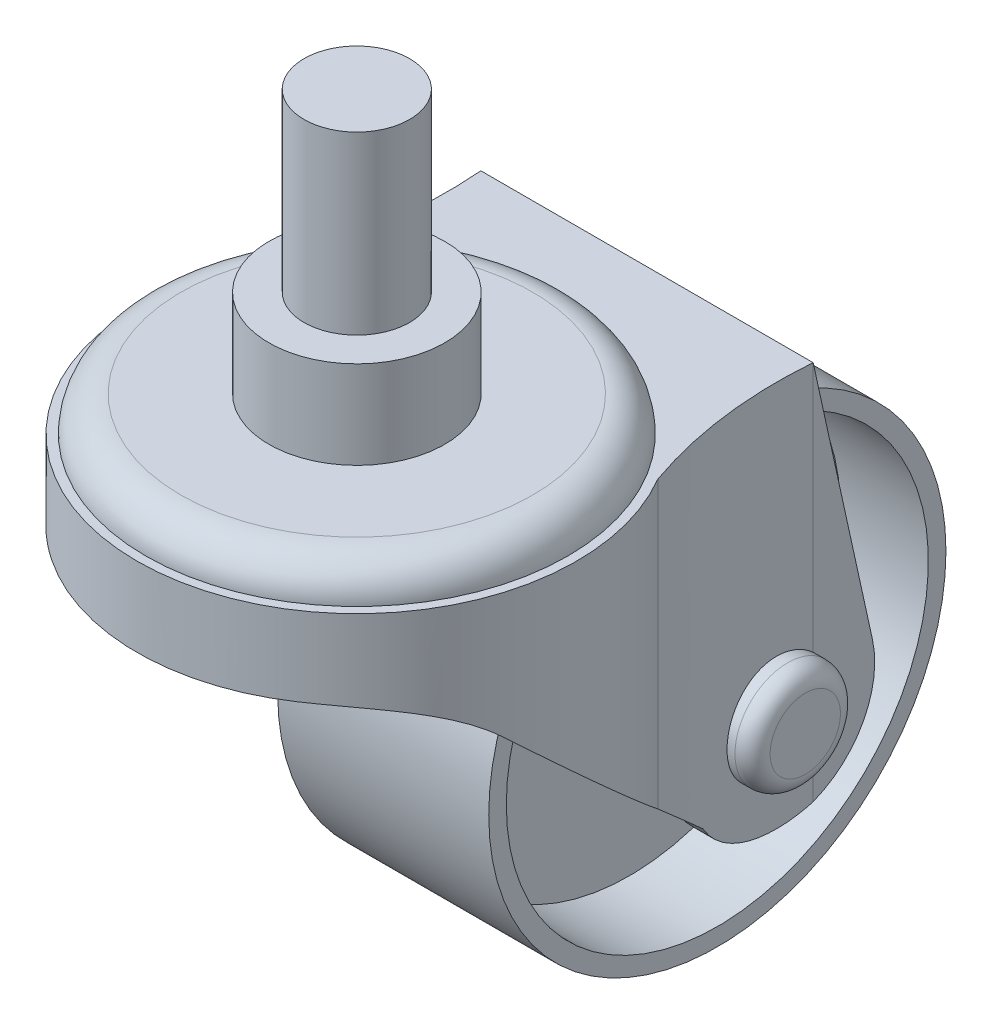
SolidWorks part; units mm, degrees
ref_plane "Plan de face" through (0, 0, 0) normal (0, 0, 1) x (1, 0, 0)
ref_plane "Plan de dessus" through (0, 0, 0) normal (0, 1, 0) x (1, 0, 0)
ref_plane "Plan de droite" through (0, 0, 0) normal (1, 0, 0) x (0, 0, -1)
sketch "Esquisse1" plane through (0, 0, 0) normal (1, 0, 0) x (0, 0, -1)
  line L0 (5.3714, 1.1823) -> (2, 16.5)
  line L1 (2, 16.5) -> (-27, 16.5)
  line L3 (-27, 16.5) -> (-27, 12)
  line L4 (-27, 12) -> (-24.8813, 12)
  line L5 (-18.135, 9.3815) -> (-4.6413, -2.951)
  arc A0 (-4.6413, -2.951) -> (5.3714, 1.1823) centre (0, 0) ccw
  arc A1 (-18.135, 9.3815) -> (-24.8813, 12) centre (-24.8813, 2) ccw
  point P11 (-21, 12)
  dimension "D1" = 11
  dimension "D2" = 16.5
  dimension "D7" = 10
  dimension "D3" = 2
  dimension "D4" = 29
  dimension "D5" = 4.5
  dimension "D6" = 6
extrude "BASE" add sketch "Esquisse1" along normal blind 25
sketch "Esquisse2" plane through (0, 16.5, 0) normal (0, 1, 0) x (1, 0, 0)
  line L0 (0, -27) -> (25, 5.6712) construction
  line L1 (12.5, -10.6644) -> (12.5, -22.6672) construction
  line L2 (25, -27) -> (0, -27) construction
  line L3 (12.4486, -2) -> (21.9486, -2) construction
  line L4 (25, 2) -> (0, 2) construction
  line L5 (21.9486, -2) -> (21.9486, 2) construction
  line L6 (21.9486, 2) -> (21.9486, 5.6712)
  line L7 (0, 5.6712) -> (25, 5.6712)
  line L8 (0, 5.6712) -> (0, -27)
  line L9 (0, -27) -> (25, -27)
  line L10 (25, 5.6712) -> (25, -27)
  line L11 (0, 5.6712) -> (25, -27) construction
  line L12 (0, -27) -> (25, 5.6712) construction
  line L13 (3.0514, 2) -> (3.0514, 5.6712)
  arc A0 (1.7322, -8.1515) -> (23.2678, -8.1515) centre (12.5, -14.5) ccw
  spline S0 degree 2 poles (23.2678, -8.1515) (21.5292, -3.1901) (21.9486, 2) knots 0 0 0 1 1 1
  spline S1 degree 2 poles (1.7322, -8.1515) (3.4708, -3.1901) (3.0514, 2) knots 0 0 0 1 1 1
  line M1 (0, 2) -> (0, -27)
  line M2 (0, -27) -> (25, -27)
  line M3 (25, -27) -> (25, 2)
  line M4 (25, 2) -> (0, 2)
  dimension "D1" = 25
  dimension "D2" = 9.5
  dimension "D3" = 4
extrude "VIDE BASE" cut sketch "Esquisse2" against normal blind 25 contours S0 A0 L10 M4 | L10 L7 L6 M4 | L13 L7 L8 M4 | A0 S1 M4 M1 | A0 L8 M2 | A0 L9 M3 region at (23.6921, 16.5, 3.4682) region at (23.4743, 16.5, -3.8356) region at (1.5257, 16.5, -3.8356) region at (1.3079, 16.5, 3.4682) region at (22.2079, 16.5, 24.2079) region at (2.7921, 16.5, 24.2079)
sketch "Esquisse3" plane through (0, 16.5, 0) normal (0, 1, 0) x (1, 0, 0)
  line L0 (25, -14.5) -> (0, -14.5) construction
  arc A0 (1.7322, -8.1515) -> (23.2678, -8.1515) centre (12.5, -14.5) ccw construction
  circle A1 centre (12.5, -14.5) radius 12
  dimension "D1" = 24
ref_plane "AXE DE SYM" through (12.5, 0, 0) normal (-1, 0, 0) x (0, 0, 1)
sketch "Esquisse4" plane through (12.5, 0, 0) normal (-1, 0, 0) x (0, 0, 1)
  line L0 (14.5, 16.5) -> (14.5, 33.5)
  line L1 (14.5, 33.5) -> (17.5, 33.5)
  line L2 (17.5, 33.5) -> (17.5, 23.5)
  line L3 (17.5, 23.5) -> (19.5, 23.5)
  line L4 (19.5, 23.5) -> (19.5, 18.5)
  line L5 (19.5, 18.5) -> (26.5, 18.5)
  line L6 (26.5, 18.5) -> (26.5, 16.5)
  line L7 (26.5, 16.5) -> (14.5, 16.5)
  dimension "D1" = 12
  dimension "D2" = 2
  dimension "D3" = 5
  dimension "D4" = 10
  dimension "D5" = 3
  dimension "D6" = 2
revolve "VIS" add sketch "Esquisse4" angle 360 about L0
fillet "Congé2" radius 2 1 edges at (12.5, 18.5, 2.5)
sketch "Esquisse6" plane through (0, 0, 0) normal (0, 1, 0) x (1, 0, 0)
  line L0 (12.5, 17.3057) -> (12.5, -17.3057) construction
  line L1 (4.0514, 5.5) -> (4.0514, -5.6095)
  line L2 (21.9486, 5.5) -> (3.0514, 5.5) construction
  line L3 (4.0514, 5.5) -> (20.9486, 5.5)
  line L4 (20.9486, 5.5) -> (20.9486, -5.6095)
  line L5 (3.0514, 5.5) -> (3.0514, 2) construction
  line L6 (21.9486, 2) -> (21.9486, 5.5) construction
  arc A0 (4.0514, -5.6095) -> (20.9486, -5.6095) centre (12.5, -13.6923) ccw
  arc A1 (5.5374, -24.8813) -> (19.4626, -24.8813) centre (12.5, -14.5) ccw construction
  arc A2 (1.7322, -8.1515) -> (0.5402, -18.135) centre (12.5, -14.5) ccw construction
  dimension "D1" = 1
  dimension "D2" = 1
extrude "VIDE BASE  2 " cut sketch "Esquisse6" along normal blind 14 and the other way blind 14
sketch "Esquisse7" plane through (12.5, 0, 0) normal (-1, 0, 0) x (0, 0, 1)
  circle A0 centre (0, 0) radius 3
  dimension "D1" = 6
extrude "AXE ROUE" add sketch "Esquisse7" along normal blind 11 and the other way blind 11
fillet "CONGE VIS 1" radius 1 1 edges at (23.5, 0, 3)
fillet "CONGE VIS 2" radius 1 1 edges at (1.5, 0, 3)
sketch "Esquisse9" plane through (0, 0, 0) normal (0, 1, 0) x (1, 0, 0)
  line L0 (18.5, -4) -> (18.5, -3)
  line L1 (12.5, 17.3057) -> (12.5, -17.3057) construction
  line L2 (6.5, -4) -> (6.5, -3)
  line L3 (6.5, -4) -> (11.5, -4)
  line L4 (11.5, -4) -> (11.5, -12)
  line L5 (11.5, -12) -> (6.5, -12)
  line L6 (6.5, -12) -> (6.5, -13)
  line L7 (6.5, -13) -> (18.5, -13)
  line L8 (12.5, -13) -> (12.5, 17.3057) construction
  line L9 (4.0514, -3) -> (20.9486, -3) construction
  line L10 (6.5, -3) -> (18.5, -3)
  line L11 (18.5, -4) -> (13.5, -4)
  line L12 (13.5, -4) -> (13.5, -12)
  line L13 (4.0514, -3) -> (20.9486, -3) construction
  line L15 (18.5, -12) -> (18.5, -13)
  line L16 (13.5, -12) -> (18.5, -12)
  line L17 (7.7934, 0) -> (17.0979, 0) construction
  point P1 (12.5, -3)
  point P3 (12.5, 0)
  point P13 (6.5, -3)
  dimension "D1" = 10
  dimension "D2" = 1
  dimension "D5" = 1
revolve "ROUE" add sketch "Esquisse9" angle 360 about L17
